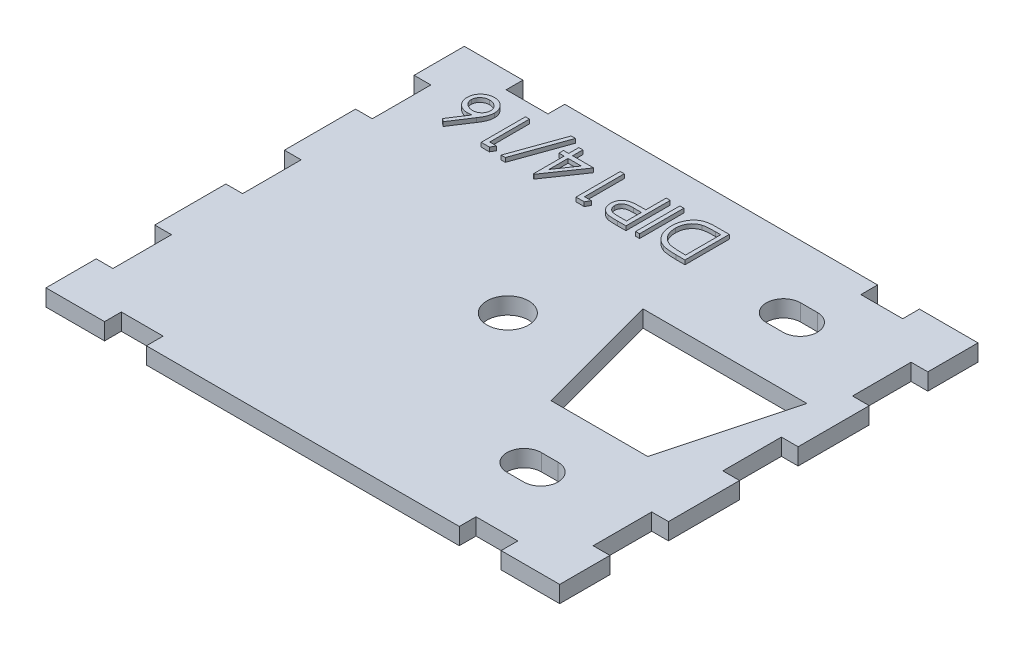
SolidWorks part; units mm, degrees
ref_plane "Front Plane" through (0, 0, 0) normal (0, 0, 1) x (1, 0, 0)
ref_plane "Top Plane" through (0, 0, 0) normal (0, 1, 0) x (1, 0, 0)
ref_plane "Right Plane" through (0, 0, 0) normal (1, 0, 0) x (0, 0, -1)
sketch "Sketch2" plane through (0, 0, 0) normal (0, 1, 0) x (1, 0, 0)
  line L1 (-50, 25) -> (50, 25)
  line L2 (-50, 25) -> (-50, -25)
  line L3 (-50, -25) -> (50, -25)
  line L4 (50, 25) -> (50, -25)
  line L5 (-50, 25) -> (50, -25) construction
  line L6 (-50, -25) -> (50, 25) construction
  point P0 (0, 0)
  dimension "D1" = 100
  dimension "D2" = 50
extrude "Boss-Extrude1" add sketch "Sketch2" along normal blind 2
sketch "Sketch12" plane through (0, 2, 0) normal (0, 1, 0) x (1, 0, 0)
  line L0 (-50, -25) -> (50, -25) construction
  line L1 (-40.2, -25) -> (-50, -25)
  line L2 (-40.2, -25) -> (-40.2, 25)
  line L3 (-40.2, 25) -> (-50, 25)
  line L4 (-50, -25) -> (-50, 25)
  line L5 (-50, -25) -> (50, -25) construction
  line L6 (41.2, -25) -> (50, -25)
  line L7 (41.2, -25) -> (41.2, 25)
  line L8 (41.2, 25) -> (50, 25)
  line L9 (50, -25) -> (50, 25)
extrude "Cut-Extrude8" cut sketch "Sketch12" against normal blind 6
sketch "Sketch13" plane through (0, 2, 0) normal (0, 1, 0) x (1, 0, 0)
  line L1 (-28.2, 19) -> (-30.2, 19)
  line L2 (-28.2, 19) -> (-28.2, 12)
  line L3 (-28.2, 12) -> (-30.2, 12)
  line L4 (-30.2, 19) -> (-30.2, 12)
  line L5 (-28.2, 3.5) -> (-30.2, 3.5)
  line L6 (-28.2, 3.5) -> (-28.2, -3.5)
  line L7 (-28.2, -3.5) -> (-30.2, -3.5)
  line L8 (-30.2, 3.5) -> (-30.2, -3.5)
  line L9 (-28.2, -12) -> (-30.2, -12)
  line L10 (-28.2, -12) -> (-28.2, -19)
  line L11 (-28.2, -19) -> (-30.2, -19)
  line L12 (-30.2, -12) -> (-30.2, -19)
  line L13 (29.2, 19) -> (31.2, 19)
  line L14 (29.2, 19) -> (29.2, 12)
  line L15 (29.2, 12) -> (31.2, 12)
  line L16 (31.2, 19) -> (31.2, 12)
  line L17 (29.2, 3.5) -> (31.2, 3.5)
  line L18 (29.2, 3.5) -> (29.2, -3.5)
  line L19 (29.2, -3.5) -> (31.2, -3.5)
  line L20 (31.2, 3.5) -> (31.2, -3.5)
  line L21 (29.2, -12) -> (31.2, -12)
  line L22 (29.2, -12) -> (29.2, -19)
  line L23 (29.2, -19) -> (31.2, -19)
  line L24 (31.2, -12) -> (31.2, -19)
  line L25 (-40.2, -25) -> (41.2, -25) construction
  line L26 (-23.2, 25) -> (-18.2, 25)
  line L27 (41.2, 25) -> (-40.2, 25) construction
  line L28 (-40.2, -25) -> (41.2, -25) construction
  line L29 (41.2, 25) -> (-40.2, 25) construction
  line L30 (-40.2, -25) -> (41.2, -25) construction
  line L31 (41.2, 25) -> (31.2, 25)
  line L32 (41.2, 25) -> (41.2, -25)
  line L33 (41.2, -25) -> (31.2, -25)
  line L34 (31.2, 25) -> (31.2, -25)
  line L35 (41.2, 25) -> (-40.2, 25) construction
  line L36 (-40.2, -25) -> (-30.2, -25)
  line L37 (-40.2, -25) -> (-40.2, 25)
  line L38 (-40.2, 25) -> (-30.2, 25)
  line L39 (-30.2, -25) -> (-30.2, 25)
  line L40 (-23.2, 25) -> (-23.2, 23)
  line L41 (-23.2, 23) -> (-18.2, 23)
  line L42 (-18.2, 25) -> (-18.2, 23)
  line L43 (-23.2, -25) -> (-18.2, -25)
  line L44 (-23.2, -25) -> (-23.2, -23)
  line L45 (-23.2, -23) -> (-18.2, -23)
  line L46 (-18.2, -25) -> (-18.2, -23)
  line L47 (24.2, -25) -> (19.2, -25)
  line L48 (24.2, -25) -> (24.2, -23)
  line L49 (24.2, -23) -> (19.2, -23)
  line L50 (19.2, -25) -> (19.2, -23)
  line L51 (24.2, 25) -> (19.2, 25)
  line L52 (24.2, 25) -> (24.2, 23)
  line L53 (24.2, 23) -> (19.2, 23)
  line L54 (19.2, 25) -> (19.2, 23)
  point P24 (29.2, 0)
  point P30 (30.2, 3.5)
  line M32 (41.2, -25) -> (41.2, 25)
  line M41 (41.2, 25) -> (-40.2, 25)
  line M42 (-40.2, 25) -> (-40.2, -25)
  line M47 (-40.2, -25) -> (41.2, -25)
  dimension "D1" = 2
  dimension "D2" = 2
  dimension "D3" = 2
  dimension "D4" = 2
  dimension "D5" = 2
  dimension "D6" = 2
  dimension "D7" = 57.4
  dimension "D8" = 57.4
  dimension "D9" = 57.4
  dimension "D10" = 7
  dimension "D11" = 7
  dimension "D12" = 7
  dimension "D13" = 7
  dimension "D14" = 7
  dimension "D15" = 7
  dimension "D16" = 5
  dimension "D17" = 2
  dimension "D18" = 5
  dimension "D19" = 6
  dimension "D20" = 8.5
  dimension "D21" = 8.5
  dimension "D22" = 6
  dimension "D23" = 6
  dimension "D24" = 8.5
  dimension "D25" = 8.5
  dimension "D26" = 6
  dimension "D27" = 5
  dimension "D28" = 5
  dimension "D29" = 2
  dimension "D30" = 2
  dimension "D31" = 5
  dimension "D32" = 5
  dimension "D33" = 5
  dimension "D34" = 5
  dimension "D35" = 2
extrude "Cut-Extrude10" cut sketch "Sketch13" against normal blind 6 contours L5 L8 L7 L6 | L39 L12 L8 L4 M47 M41 M42 | L1 L4 L3 L2 | L50 L48 L49 M47 | L24 L21 L22 L23 | L20 L17 L18 L19 | L16 L13 L14 L15 | L54 L53 L52 M41 | L9 L12 L11 L10 | L34 L16 L20 L24 M41 M47 M32 | L26 L42 L41 L40 | L45 L46 L43 L44 region at (-29.2, 2, -15.5) region at (-35.2, 2, 0) region at (-29.2, 2, 0) region at (-29.2, 2, 15.5) region at (21.7, 2, -24) region at (36.2, 2, 0) region at (21.7, 2, 24) region at (30.2, 2, -15.5) region at (30.2, 2, 0) region at (30.2, 2, 15.5)
sketch "Sketch15" plane through (0, 0, 0) normal (0, -1, 0) x (1, 0, 0)
  line L0 (24.2, 23) -> (19.2, 23) construction
  line L16 (20.7242, -7.5) -> (20.7242, -8.5)
  line L17 (20.7242, -7.5) -> (25.936, -7.5)
  line L18 (25.936, -7.5) -> (22.4527, 5.5)
  line L19 (22.4527, 5.5) -> (12.4527, 5.5)
  line L20 (12.4527, 5.5) -> (8.9693, -7.5)
  line L21 (8.9693, -7.5) -> (14.1811, -7.5)
  line L22 (14.1811, -7.5) -> (14.1811, -8.5)
  line L23 (14.1811, -8.5) -> (7.6661, -8.5)
  line L24 (7.6661, -8.5) -> (11.6853, 6.5)
  line L25 (11.6853, 6.5) -> (23.22, 6.5)
  line L26 (23.22, 6.5) -> (27.2392, -8.5)
  line L27 (27.2392, -8.5) -> (20.7242, -8.5)
  line L28 (20.7242, -8.5) -> (14.1811, -8.5)
  line L29 (14.1811, -7.5) -> (20.7242, -7.5)
  line L31 (29.2, 12) -> (29.2, 19) construction
  dimension "D4" = 16.5
  dimension "D18" = 11.5347
  dimension "D19" = 15.5291
  dimension "D20" = 15.5291
  dimension "D21" = 13.4586
  dimension "D22" = 13.4586
  dimension "D23" = 10
  dimension "D24" = 5.2118
  dimension "D25" = 5.2118
  dimension "D26" = 6.515
  dimension "D27" = 6.515
  dimension "D28" = 1
  dimension "D29" = 105
  dimension "D30" = 105
  dimension "D31" = 75
  dimension "D32" = 75
  dimension "D33" = 5.98
  dimension "D34" = 1
extrude "Cut-Extrude13" cut sketch "Sketch15" against normal blind 10 contours L21 L29 L17 L18 L19 L20 | L27 L26 L25 L24 L23 L22 L21 L20 L19 L18 L17 L16 | L29 L22 L28 L16 region at (23.3301, 0, -7.7466) region at (17.4527, 0, -1.5597) region at (17.4527, 0, -8)
sketch "Sketch16" plane through (0, 0, 0) normal (0, -1, 0) x (-1, 0, 0)
  circle A0 centre (0, 0) radius 2.5
  dimension "D1" = 5
extrude "Cut-Extrude14" cut sketch "Sketch16" against normal blind 10 contours A0
sketch "Sketch17" plane through (0, 0, 0) normal (0, -1, 0) x (-1, 0, 0)
  line L0 (-18.4527, 18.55) -> (-16.4527, 18.55)
  line L1 (-18.4527, 14.45) -> (-16.4527, 14.45)
  line L2 (-27.2392, 8.5) -> (-7.6661, 8.5) construction
  line L3 (-18.4527, -12.45) -> (-16.4527, -12.45)
  line L4 (-11.6853, -6.5) -> (-23.22, -6.5) construction
  line L5 (-18.4527, -16.55) -> (-16.4527, -16.55)
  circle A0 centre (-17.4527, -14.5) radius 2.05
  circle A1 centre (-17.4527, 16.5) radius 2.05
  circle A2 centre (-16.4527, 16.5) radius 2.05
  circle A3 centre (-18.4527, 16.5) radius 2.05
  circle A4 centre (-16.4527, -14.5) radius 2.05
  circle A5 centre (-18.4527, -14.5) radius 2.05
  dimension "D1" = 4.1
  dimension "D2" = 4.1
  dimension "D9" = 1
  dimension "D3" = 8
  dimension "D4" = 9.7866
  dimension "D5" = 9.7866
  dimension "D6" = 5.7673
  dimension "D7" = 5.7673
  dimension "D8" = 8
  dimension "D10" = 1
  dimension "D11" = 0
  dimension "D12" = 0
  dimension "D13" = 1
  dimension "D14" = 1
  dimension "D15" = 0
  dimension "D16" = 0
extrude "Cut-Extrude15" cut sketch "Sketch17" against normal blind 3.5 contours A5 A0 L3 | A5 A4 A0 | A4 L3 A0 | A5 L5 A0 | A5 A0 A4 | A4 A0 L5 | A4 A0 | A5 A4 A0 | A4 A5 | A0 A5 A4 | A5 A0 | A3 A1 L0 | A3 A2 A1 | A2 L0 A1 | A3 L1 A1 | A3 A1 A2 | A2 A1 L1 | A2 A1 | A3 A2 A1 | A2 A3 | A1 A3 A2 | A3 A1 region at (19.579, 0, -16.5) region at (17.9527, 0, -18.5315) region at (16.9527, 0, -18.5315) region at (17.4527, 0, -18.454) region at (17.9527, 0, -14.4685) region at (18.6548, 0, -16.5) region at (15.3263, 0, -16.5) region at (16.2506, 0, -16.5) region at (16.9527, 0, -14.4685) region at (17.4527, 0, -14.546) region at (17.4527, 0, -16.5) region at (19.579, 0, 14.5) region at (17.9527, 0, 12.4685) region at (16.9527, 0, 12.4685) region at (17.4527, 0, 12.546) region at (17.9527, 0, 16.5315) region at (18.6548, 0, 14.5) region at (15.3263, 0, 14.5) region at (16.2506, 0, 14.5) region at (16.9527, 0, 16.5315) region at (17.4527, 0, 16.454) region at (17.4527, 0, 14.5)
sketch "Sketch22" plane through (0, 2, 0) normal (0, 1, 0) x (1, 0, 0)
  line L0 (-24.5837, 20.8621) -> (9.284, 20.8621) construction
  text T0 "DIP14/16" font "Century Gothic" height in points 20
extrude "Boss-Extrude4" add sketch "Sketch22" along normal blind 0.5
